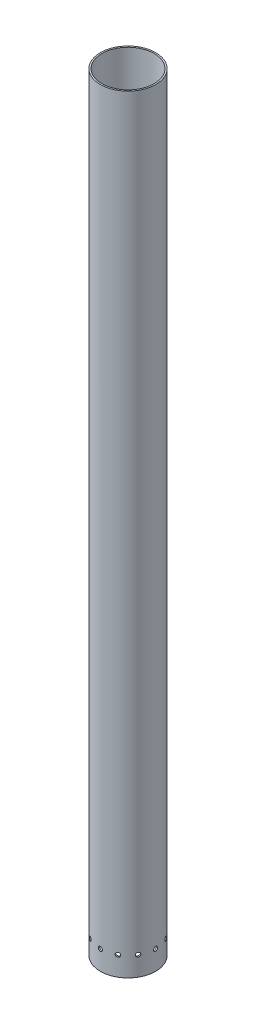
SolidWorks part; units mm, degrees
material "6063-T6"
ref_plane "Front Plane" through (0, 0, 0) normal (0, 0, 1) x (1, 0, 0)
ref_plane "Top Plane" through (0, 0, 0) normal (0, 1, 0) x (1, 0, 0)
ref_plane "Right Plane" through (0, 0, 0) normal (1, 0, 0) x (0, 0, -1)
sketch "Sketch1" plane through (0, 0, 0) normal (0, 0, 1) x (1, 0, 0)
  line L0 (0, 0) -> (0, 45.6531) construction
  line L1 (25.5143, 52.2108) -> (26.9875, 52.2108)
  line L2 (25.5143, 52.2108) -> (25.5143, -697.0892)
  line L3 (25.5143, -697.0892) -> (26.9875, -697.0892)
  line L4 (26.9875, 52.2108) -> (26.9875, -697.0892)
revolve "Revolve1" add sketch "Sketch1" angle 360 about L0
ref_plane "Plane1" through (0, 0, -26.9875) normal (0, 0, -1) x (-1, 0, 0)
sketch "Sketch2" plane through (0, 0, -26.9875) normal (0, 0, -1) x (-1, 0, 0)
  point P0 (0, -678.0392)
  point P2 (0, 0)
  point P3 (0, -676.7692)
  point P4 (0.1588, -677.2448)
  point P5 (0, -676.7692)
hole_wizard "#10-32 Tapped Hole1" positions "Sketch2" profile "Sketch3" tap size "#10-32" standard "ANSI Inch"
sketch "Sketch3" plane through (0, -678.0392, -26.9875) normal (1, 0, 0) x (0, 1, 0)
  line L0 (0, 0) -> (0, 15.1833)
  line L1 (0, 15.1833) -> (2.0193, 13.97)
  line L2 (2.0193, 13.97) -> (2.0193, 0)
  line L5 (2.0193, 0) -> (0, 0)
  line L10 (0, 15.1833) -> (-2.0193, 13.97) construction
  line L11 (0, -6.35) -> (0, 107.95) construction
  dimension "Tap Drill Dia." = 4.0386
  dimension "Tap Drill Depth" = 13.97
  dimension "Drill Angle" = 118
pattern_circular "CirPattern1" count 12 over 360 about axis through (0, 0, 0) along (0, -1, 0) of "#10-32 Tapped Hole1" reverse direction yes
